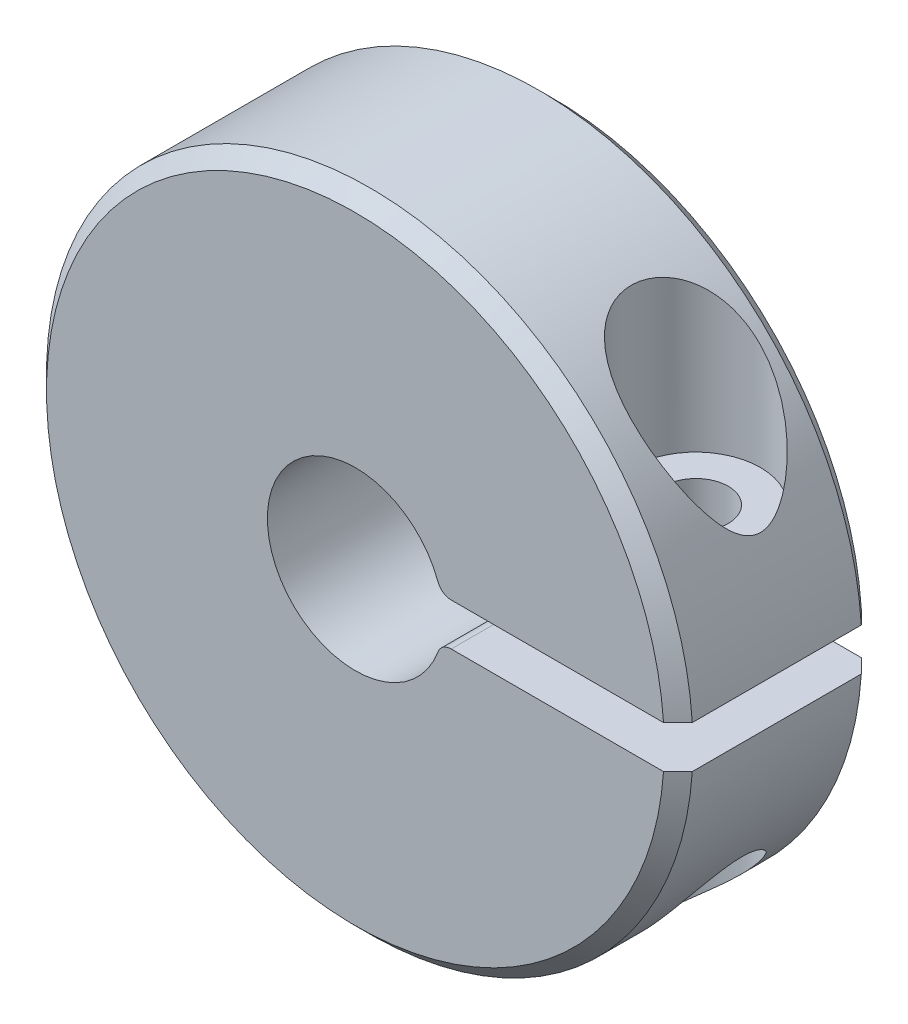
SolidWorks part; units mm, degrees
ref_plane "Front Plane" through (0, 0, 0) normal (0, 0, 1) x (1, 0, 0)
ref_plane "Top Plane" through (0, 0, 0) normal (0, 1, 0) x (1, 0, 0)
ref_plane "Right Plane" through (0, 0, 0) normal (1, 0, 0) x (0, 0, -1)
sketch "Sketch1" plane through (0, 0, 0) normal (0, 0, 1) x (1, 0, 0)
  line L0 (3.1, 0) -> (7.291, 0) construction
  line L1 (3.0198, -0.75) -> (11.4054, -0.75)
  line L2 (3.0198, 0.75) -> (11.4054, 0.75)
  line L3 (3.1, 0.75) -> (7.291, 0.75) construction
  line L4 (3.1, -0.75) -> (7.291, -0.75) construction
  arc A0 (3.0198, 0.75) -> (3.0198, -0.75) centre (0, 0) ccw
  arc A1 (11.4054, 0.75) -> (11.4054, -0.75) centre (0, 0) ccw
  dimension "D1" = 6.223
  dimension "D2" = 22.86
  dimension "D5" = 4.191
  dimension "D3" = 0.75
  dimension "D4" = 0.75
extrude "Boss-Extrude1" add sketch "Sketch1" along normal blind 6.985
sketch "Sketch2" plane through (0, 0.75, 0) normal (0, -1, 0) x (1, 0, 0)
  line L0 (8.2304, 0) -> (8.2304, 3.175) construction
  line L1 (-11.43, 0) -> (11.4054, 0) construction
  line L2 (8.2304, 3.175) -> (11.4054, 3.4925) construction
  line L3 (11.4054, 6.985) -> (11.4054, 0) construction
  circle A0 centre (8.2304, 3.175) radius 1.143
  dimension "D3" = 2.286
  dimension "D1" = 3.175
  dimension "D2" = 3.175
extrude "Cut-Extrude1" cut sketch "Sketch2" against normal through all both and the other way through all
ref_plane "Plane1" through (0, 4.179, 0) normal (0, -1, 0) x (-1, 0, 0)
sketch "Sketch3" plane through (0, 4.179, 0) normal (0, -1, 0) x (-1, 0, 0)
  circle A0 centre (-8.2304, -3.175) radius 2.286
  dimension "D1" = 4.572
extrude "Cut-Extrude2" cut sketch "Sketch3" against normal through all
sketch "Sketch4" plane through (0, 0, 0) normal (0, 0, -1) x (-1, 0, 0)
  line L0 (3.1115, 0) -> (11.43, 0)
  line L1 (3.1115, 0) -> (0, 0) construction
  line L2 (-3.0198, -0.75) -> (-11.4054, -0.75)
  line L3 (-11.4054, 0.75) -> (-3.0198, 0.75)
  line L5 (-11.4054, 0.75) -> (-3.0198, 0.75)
  arc A2 (-3.0198, -0.75) -> (-3.0198, 0.75) centre (0, 0) ccw
  arc A3 (-11.4054, -0.75) -> (-11.4054, 0.75) centre (0, 0) ccw
  arc A4 (3.1115, 0) -> (-3.0198, 0.75) centre (0, 0) ccw
  arc A5 (11.43, 0) -> (-11.4054, 0.75) centre (0, 0) ccw
  dimension "D1" = 0
extrude "Boss-Extrude2" add sketch "Sketch4" along normal blind 1.27
sketch "Sketch5" plane through (0, 0, -1.27) normal (0, 0, -1) x (-1, 0, 0)
  circle A0 centre (0, 0) radius 3.1115
  circle A1 centre (0, 0) radius 11.43
  arc A2 (-11.4054, -0.75) -> (11.43, 0) centre (0, 0) ccw construction
extrude "Boss-Extrude3" add sketch "Sketch5" along normal blind 2.54
ref_plane "Plane2" through (0, -3.75, 0) normal (0, 1, 0) x (1, 0, 0)
sketch "Sketch29" plane through (0, -3.75, 0) normal (0, 1, 0) x (1, 0, 0)
  circle A0 centre (8.2304, -3.175) radius 1.778
  dimension "D1" = 3.556
extrude "Cut-Extrude9" cut sketch "Sketch29" against normal through all
chamfer "Chamfer3" distance 0.508 angle 80 1 edges at (8.2304, -3.75, 4.953) first distance on face at (8.2304, -3.75, 4.953)
chamfer "Chamfer4" distance 0.508 angle 45 1 edges at (-11.43, 0, 6.985)
fillet "Fillet1" radius 0.5 4 edges at (3.0198, 0.75, 2.8575) (3.0198, -0.75, 3.4925) (-11.43, 0, -0.635) (-3.1115, 0, -0.635)
sketch "Sketch30" plane through (0, 0, -3.81) normal (0, 0, -1) x (-1, 0, 0)
  circle A0 centre (0, 0) radius 16.9012
extrude "Cut-Extrude10" cut sketch "Sketch30" against normal up to surface (3.81 mm away) up to face at (-1.8103, -2.2489, 0)
chamfer "Chamfer5" distance 0.5 angle 45 1 edges at (-11.43, 0, 0)
equation "\"90g\"=10"
